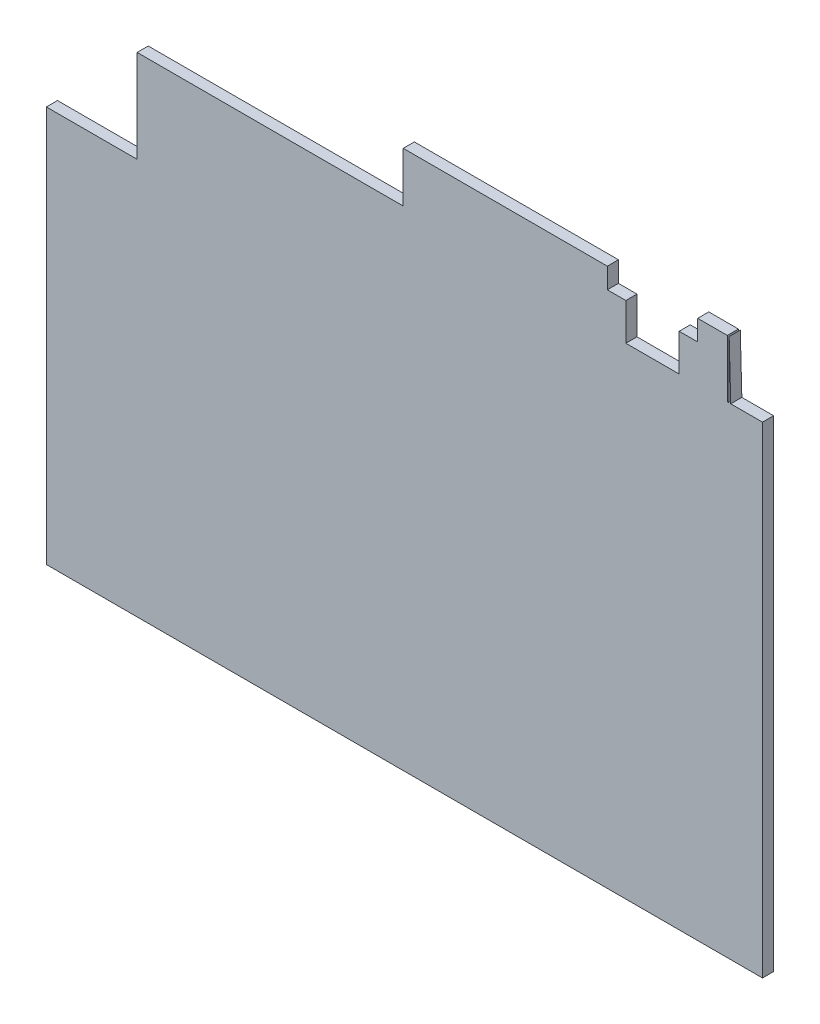
SolidWorks part; units mm, degrees
material "ABS"
ref_plane "Front Plane" through (0, 0, 0) normal (0, 0, 1) x (1, 0, 0)
ref_plane "Top Plane" through (0, 0, 0) normal (0, 1, 0) x (1, 0, 0)
ref_plane "Right Plane" through (0, 0, 0) normal (1, 0, 0) x (0, 0, -1)
sketch "Sketch1" plane through (0, 0, 0) normal (0, 0, 1) x (1, 0, 0)
  line L0 (28.5714, 236.0602) -> (28.5714, 237.0518)
  line L1 (28.5714, 277.1048) -> (28.5714, -22.8952) construction
  line L2 (28.5714, 237.0518) -> (5.4155, 237.0518)
  line L3 (5.4155, 237.0518) -> (4.5714, 268.1048)
  line L4 (4.5714, 268.1048) -> (-12.4286, 268.1048)
  line L5 (-12.4286, 268.1048) -> (-12.4286, 237.0518)
  line L6 (-12.4286, 237.0518) -> (-38.2166, 237.0518)
  line L7 (-38.2166, 237.0518) -> (-38.2166, 268.1048)
  line L8 (-221.4286, 268.1048) -> (28.5714, 268.1048) construction
  line L9 (-38.2166, 268.1048) -> (-171.4286, 268.1048)
  line L10 (-171.4286, 268.1048) -> (-171.4286, 241.1048)
  line L11 (-171.4286, 241.1048) -> (-370.1235, 241.1048)
  line L12 (-370.1235, 241.1048) -> (-370.1235, -22.8952)
  line L13 (-370.1235, -22.8952) -> (28.5714, -22.8952)
  line L14 (28.5714, -22.8952) -> (28.5714, 236.0602)
extrude "Boss-Extrude1" add sketch "Sketch1" along normal blind 6
sketch "Sketch2" plane through (0, 0, 6) normal (0, 0, 1) x (1, 0, 0)
  line L1 (-370.1235, 241.1048) -> (-315.1235, 241.1048)
  line L2 (-370.1235, 241.1048) -> (-370.1235, 191.1048)
  line L3 (-370.1235, 191.1048) -> (-315.1235, 191.1048)
  line L4 (-315.1235, 241.1048) -> (-315.1235, 191.1048)
  dimension "D1" = 55
  dimension "D2" = 50
extrude "Cut-Extrude1" cut sketch "Sketch2" against normal blind 10
sketch "Sketch3" plane through (0, 0, 6) normal (0, 0, 1) x (1, 0, 0)
  line L0 (4.5714, 268.1048) -> (-12.4286, 268.1048) construction
  line L1 (28.5714, -22.8952) -> (22.5714, -22.8952)
  line L2 (28.5714, -22.8952) -> (28.5714, 268.1048)
  line L3 (28.5714, 268.1048) -> (22.5714, 268.1048)
  line L4 (22.5714, -22.8952) -> (22.5714, 268.1048)
  line L5 (-171.4286, 241.1048) -> (-315.1235, 241.1048) construction
  line L6 (-370.1235, -22.8952) -> (-364.1235, -22.8952)
  line L7 (-370.1235, -22.8952) -> (-370.1235, 241.1048)
  line L8 (-370.1235, 241.1048) -> (-364.1235, 241.1048)
  line L9 (-364.1235, -22.8952) -> (-364.1235, 241.1048)
  dimension "D1" = 6
  dimension "D2" = 6
extrude "Cut-Extrude2" cut sketch "Sketch3" against normal blind 10
sketch "Sketch4" plane through (0, 0, 6) normal (0, 0, 1) x (1, 0, 0)
  line L1 (-38.2166, 268.1048) -> (-61.2166, 268.1048)
  line L2 (-38.2166, 268.1048) -> (-38.2166, 237.0518)
  line L3 (-38.2166, 237.0518) -> (-61.2166, 237.0518)
  line L4 (-61.2166, 268.1048) -> (-61.2166, 237.0518)
  line L5 (4.5714, 268.1048) -> (3.5714, 268.1048)
  line L6 (4.5714, 268.1048) -> (4.5714, 237.0518)
  line L7 (4.5714, 237.0518) -> (3.5714, 237.0518)
  line L8 (3.5714, 268.1048) -> (3.5714, 237.0518)
  dimension "D1" = 23
  dimension "D2" = 1
extrude "Cut-Extrude3" cut sketch "Sketch4" against normal blind 10
sketch "Sketch5" plane through (0, 0, 6) normal (0, 0, 1) x (1, 0, 0)
  line L1 (-61.2166, 237.0518) -> (-51.2166, 237.0518)
  line L2 (-61.2166, 237.0518) -> (-61.2166, 257.0518)
  line L3 (-61.2166, 257.0518) -> (-51.2166, 257.0518)
  line L4 (-51.2166, 237.0518) -> (-51.2166, 257.0518)
  line L5 (-12.4286, 237.0518) -> (-22.4286, 237.0518)
  line L6 (-12.4286, 237.0518) -> (-12.4286, 257.0518)
  line L7 (-12.4286, 257.0518) -> (-22.4286, 257.0518)
  line L8 (-22.4286, 237.0518) -> (-22.4286, 257.0518)
  dimension "D1" = 20
  dimension "D2" = 20
  dimension "D3" = 10
  dimension "D4" = 10
extrude "Boss-Extrude2" add sketch "Sketch5" against normal up to vertex (6 mm away) up to point (-61.2166, 268.1048, 0)
